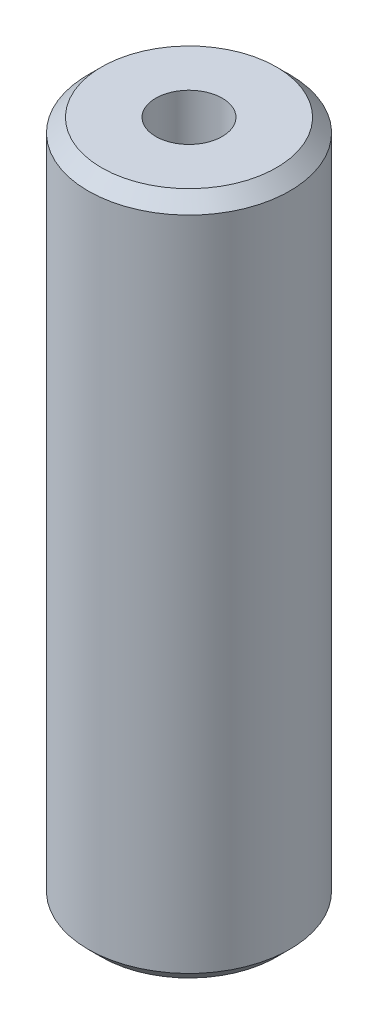
SolidWorks part; units mm, degrees
ref_plane "Front Plane" through (0, 0, 0) normal (0, 0, 1) x (1, 0, 0)
ref_plane "Top Plane" through (0, 0, 0) normal (0, 1, 0) x (1, 0, 0)
ref_plane "Right Plane" through (0, 0, 0) normal (1, 0, 0) x (0, 0, -1)
sketch "Sketch1" plane through (0, 0, 0) normal (0, 1, 0) x (1, 0, 0)
  circle A0 centre (0, 0) radius 10
  dimension "SHAFT_OD" = 20
extrude "Boss-Extrude1" add sketch "Sketch1" along normal blind 67.8072
sketch "Sketch2" plane through (0, 0, 0) normal (0, 1, 0) x (1, 0, 0)
  circle A0 centre (0, 0) radius 3.2975
  dimension "BORE_D" = 6.595
extrude "Cut-Extrude1" cut sketch "Sketch2" along normal through all
chamfer "Chamfer1" distance 1.3305 angle 45 2 edges at (0, 67.8072, 10) (0, 0, 10)
